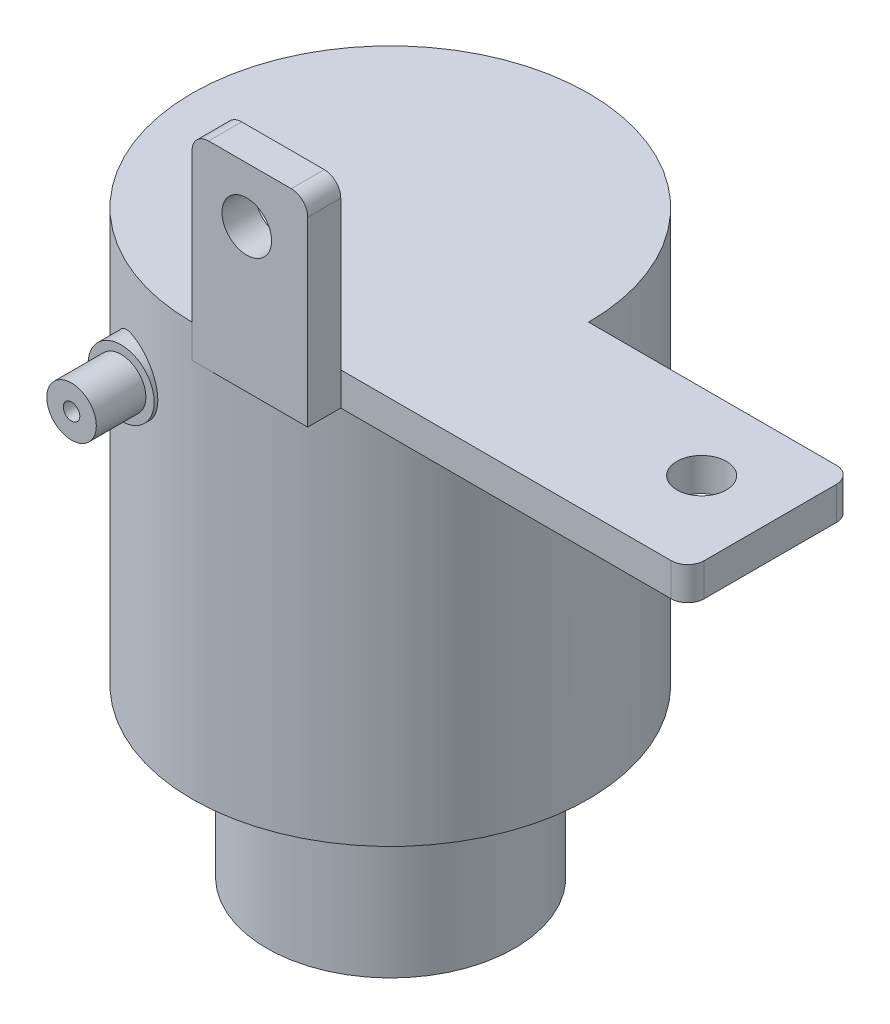
SolidWorks part; units mm, degrees
ref_plane "Alzado" through (0, 0, 0) normal (0, 0, 1) x (1, 0, 0)
ref_plane "Planta" through (0, 0, 0) normal (0, 1, 0) x (1, 0, 0)
ref_plane "Vista lateral" through (0, 0, 0) normal (1, 0, 0) x (0, 0, -1)
sketch "Croquis1" plane through (0, 0, 0) normal (0, 1, 0) x (1, 0, 0)
  line L1 (0, 0) -> (28, 0)
  line L2 (0, 0) -> (0, 10)
  line L3 (0, 10) -> (28, 10)
  line L4 (28, 0) -> (28, 10)
extrude "Saliente-Extruir1" add sketch "Croquis1" along normal blind 2 contours L2 L1 L4 L3
sketch "Croquis5" plane through (0, 0, 0) normal (0, 0, 1) x (1, 0, 0)
  line L1 (0, 0) -> (7, 0)
  line L2 (0, 0) -> (0, 12)
  line L3 (0, 12) -> (7, 12)
  line L4 (7, 0) -> (7, 12)
extrude "Saliente-Extruir5" add sketch "Croquis5" along normal blind 2
sketch "Croquis6" plane through (0, 0, 0) normal (0, 1, 0) x (1, 0, 0)
  circle A0 centre (0, 10) radius 12
extrude "Saliente-Extruir6" add sketch "Croquis6" along normal blind 2 and the other way blind 23
sketch "Croquis9" plane through (0, -23, 0) normal (0, -1, 0) x (-1, 0, 0)
  circle A0 centre (-0.0852, 9.9361) radius 7.5
extrude "Saliente-Extruir7" add sketch "Croquis9" along normal blind 10 contours A0
sketch "Croquis10" plane through (0, -33, 0) normal (0, -1, 0) x (1, 0, 0)
  circle A0 centre (0.0852, -9.9361) radius 6
extrude "Cortar-Extruir3" cut sketch "Croquis10" against normal blind 33
fillet "Redondeo2" radius 1 1 edges at (28, 1, -10)
fillet "Redondeo3" radius 1 1 edges at (28, 1, 0)
fillet "Redondeo4" radius 1 1 edges at (7, 12, 1)
fillet "Redondeo5" radius 1 1 edges at (0, 12, 1)
sketch "Croquis12" plane through (0, 0, 0) normal (0, 0, 1) x (1, 0, 0)
  circle A1 centre (3.3104, 8.6678) radius 1.5
extrude "Cortar-Extruir4" cut sketch "Croquis12" along normal blind 2
sketch "Croquis13" plane through (0, 0, 0) normal (0, 1, 0) x (1, 0, 0)
  circle A0 centre (23.4666, 5.3771) radius 1.5
extrude "Cortar-Extruir7" cut sketch "Croquis13" along normal blind 2
ref_axis "Eje1" through (0, -23, -10) along (0, 1, 0)
sketch "Croquis16" plane through (0, 0, 0) normal (0, 0, 1) x (1, 0, 0)
  circle A0 centre (-4.295, -3.3332) radius 2
extrude "Saliente-Extruir9" add sketch "Croquis16" along normal blind 2
sketch "Croquis17" plane through (0, 0, 0) normal (0, 0, 1) x (1, 0, 0)
  circle A1 centre (-4.295, -3.3332) radius 1.5
extrude "Saliente-Extruir10" add sketch "Croquis17" along normal blind 5
sketch "Croquis18" plane through (0, 0, 0) normal (0, 0, 1) x (1, 0, 0)
  circle A0 centre (-4.295, -3.3332) radius 0.5
extrude "Cortar-Extruir8" cut sketch "Croquis18" along normal blind 5
scale "Escala1" scale about centroid uniform scaling yes scale factor 7
